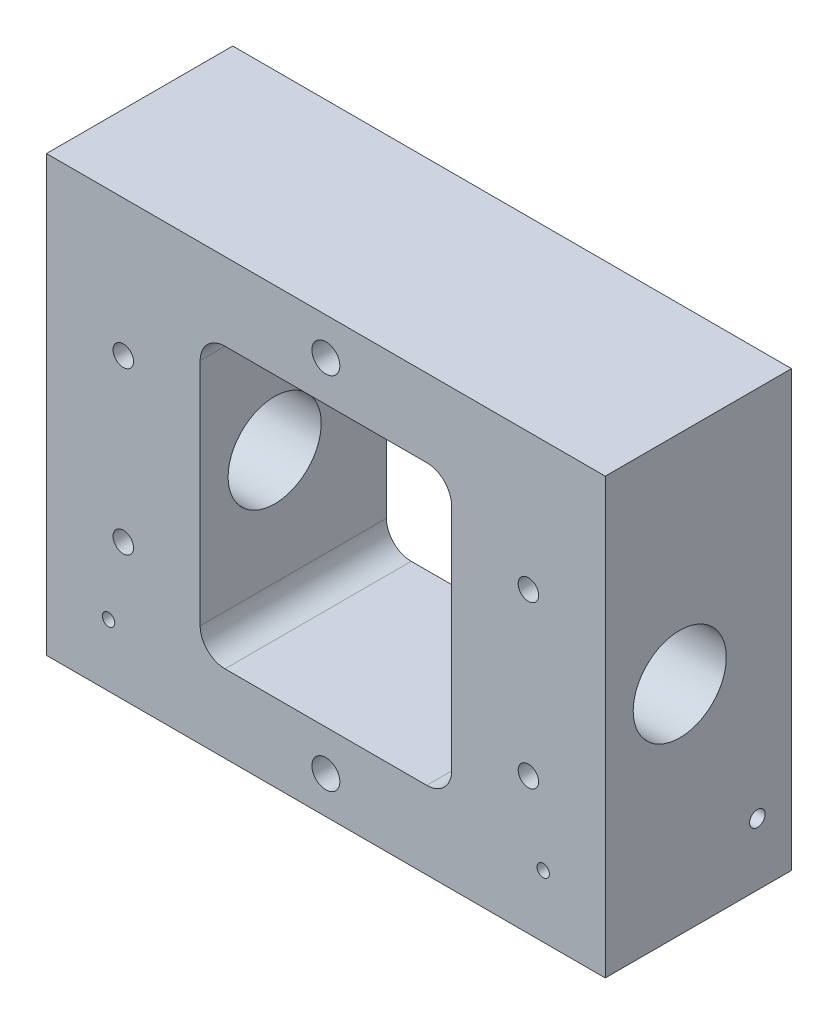
SolidWorks part; units mm, degrees
material "Lega 6061"
ref_plane "Piano frontale" through (0, 0, 0) normal (0, 0, 1) x (1, 0, 0)
ref_plane "Piano superiore" through (0, 0, 0) normal (0, 1, 0) x (1, 0, 0)
ref_plane "Piano destro" through (0, 0, 0) normal (1, 0, 0) x (0, 0, -1)
sketch "Schizzo1" plane through (0, 0, 0) normal (0, 0, 1) x (1, 0, 0)
  line L1 (0, 0) -> (90, 0)
  line L2 (0, 0) -> (0, 70)
  line L3 (0, 70) -> (90, 70)
  line L4 (90, 0) -> (90, 70)
  dimension "D1" = 90
  dimension "D2" = 70
extrude "Estrusione-Estrusione1" add sketch "Schizzo1" against normal blind 30
sketch "Schizzo2" plane through (0, 0, 0) normal (-1, 0, 0) x (0, 0, 1)
  line L0 (-30, 35) -> (0, 35) construction
  line L1 (-30, 70) -> (-30, 0) construction
  line L2 (0, 70) -> (0, 0) construction
  circle A0 centre (-12, 35) radius 7.5
  dimension "D1" = 15
  dimension "D2" = 18
extrude "Taglio-Estrusione1" cut sketch "Schizzo2" against normal through all
sketch "Schizzo3" plane through (0, 0, -30) normal (0, 0, -1) x (-1, 0, 0)
  line L0 (-94.314, 64) -> (4.9562, 64) construction
  line L2 (-90, 70) -> (0, 70) construction
  line L4 (-90, 35) -> (0, 35) construction
  line L5 (-90, 0) -> (-90, 70) construction
  line L6 (0, 70) -> (0, 0) construction
  line L7 (-94.314, 6) -> (4.9562, 6) construction
  line L8 (-45, 70) -> (-45, 0) construction
  line L9 (0, 0) -> (-90, 0) construction
  point P16 (-45, 64)
  point P17 (-45, 6)
  dimension "D1" = 6
hole_wizard "Foro lamato per Vite M4 a testa cilindrica piana-1" positions "Schizzo3D1" profile "Schizzo4" counterbore size "M4" standard "ISO" end condition through all
sketch3d "Schizzo3D1"
  line L0 (90, 70, -30) -> (0, 70, -30) construction
  point P0 (45, 64, -30)
  point P3 (45, 6, -30)
sketch "Schizzo4" plane through (45, 64, -30) normal (1, 0, 0) x (0, 1, 0)
  line L0 (0, 0) -> (0, 30)
  line L1 (0, 30) -> (2.25, 30)
  line L3 (2.25, 30) -> (2.25, 2.6)
  line L4 (2.25, 2.6) -> (4, 2.6)
  line L5 (4, 2.6) -> (4, 0)
  line L7 (4, 0) -> (0, 0)
  line L11 (0, -6.35) -> (0, 107.95) construction
  dimension "Thru Hole Dia." = 4.5
  dimension "Thru Hole Depth" = 30
  dimension "C'Bore Dia." = 8
  dimension "C'Bore Depth" = 2.6
ref_axis "Assi1" through (90, 35, -12) along (-1, 0, 0)
sketch "Schizzo14" plane through (0, 0, 0) normal (0, 0, 1) x (1, 0, 0)
  line L0 (45, 70) -> (45, 0) construction
  line L2 (61.25, 12.5) -> (28.75, 12.5)
  line L3 (65.25, 16.5) -> (65.25, 53.5)
  line L4 (90, 35) -> (0, 35) construction
  line L5 (61.25, 57.5) -> (28.75, 57.5)
  line L6 (24.75, 16.5) -> (24.75, 53.5)
  line L7 (65.25, 12.5) -> (24.75, 57.5) construction
  line L8 (65.25, 57.5) -> (24.75, 12.5) construction
  line L9 (0, 0) -> (90, 0) construction
  arc A0 (61.25, 57.5) -> (65.25, 53.5) centre (61.25, 53.5) cw
  arc A1 (65.25, 16.5) -> (61.25, 12.5) centre (61.25, 16.5) cw
  arc A2 (28.75, 12.5) -> (24.75, 16.5) centre (28.75, 16.5) cw
  arc A3 (24.75, 53.5) -> (28.75, 57.5) centre (28.75, 53.5) cw
  point P2 (45, 35)
  point P3 (45, 35)
  dimension "D1" = 4
  dimension "D2" = 45
  dimension "D3" = 40.5
  dimension "D4" = 12.5
extrude "Taglio-Estrusione4" cut sketch "Schizzo14" against normal through all
sketch "Schizzo16" plane through (0, 0, 0) normal (0, 0, 1) x (1, 0, 0)
  line L0 (45, 70) -> (45, 0) construction
  line L1 (0, 35) -> (90, 35) construction
  line L2 (0, 70) -> (0, 0) construction
  line L3 (0, 0) -> (90, 0) construction
  circle A0 centre (10, 10) radius 1
  circle A1 centre (80, 10) radius 1
  dimension "D1" = 2
  dimension "D2" = 10
  dimension "D3" = 10
extrude "Taglio-Estrusione6" cut sketch "Schizzo16" against normal through all
sketch "Schizzo17" plane through (0, 0, -30) normal (0, 0, -1) x (-1, 0, 0)
  line L0 (-45, 70) -> (-45, 0.5122) construction
  line L1 (-90, 70) -> (0, 70) construction
  line L2 (-45, 70) -> (-45, 0) construction
  line L3 (0, 35) -> (-90, 35) construction
  circle A0 centre (-10, 10) radius 8
  circle A1 centre (-80, 10) radius 8
  dimension "D1" = 16
extrude "Taglio-Estrusione8" cut sketch "Schizzo17" against normal blind 13
sketch "Schizzo18" plane through (0, 0, 0) normal (0, 0, 1) x (1, 0, 0)
  line L0 (0, 70) -> (90, 0) construction
  line L1 (90, 70) -> (0, 0) construction
  line L2 (45, 35) -> (45, 70) construction
  line L3 (12.375, 35.0996) -> (12.375, 74.2174) construction
  line L4 (24.75, 35) -> (0, 35) construction
  line L5 (24.75, 53.5) -> (24.75, 16.5) construction
  line L6 (90, 35) -> (0, 35) construction
  line L7 (90, 70) -> (0, 70) construction
  point P9 (12.375, 22)
  point P11 (45, 35)
  point P17 (12.375, 48)
  point P24 (77.625, 22)
  point P25 (77.625, 48)
  dimension "D1" = 13
hole_wizard "Foro filettato M4-1" positions "Schizzo20" profile "Schizzo19" tap size "M4" standard "ISO" end condition through all
sketch "Schizzo20" plane through (0, 0, 0) normal (0, 0, 1) x (1, 0, 0)
  point P0 (12.375, 48)
  point P3 (12.375, 22)
  point P6 (77.625, 48)
  point P9 (77.625, 22)
cosmetic thread "Filettatura del foro1" parameters "D2"=4
cosmetic thread "Filettatura del foro2" parameters "D2"=4
cosmetic thread "Filettatura del foro3" parameters "D2"=4
cosmetic thread "Filettatura del foro4" parameters "D2"=4
sketch "Schizzo19" plane through (12.375, 48, 0) normal (1, 0, 0) x (0, -1, 0)
  line L0 (0, 0) -> (0, 30)
  line L1 (0, 30) -> (1.65, 30)
  line L2 (1.65, 30) -> (1.65, 0)
  line L5 (1.65, 0) -> (0, 0)
  line L11 (0, -6.35) -> (0, 107.95) construction
  dimension "Thru Tap Drill Dia." = 3.3
  dimension "Thru Tap Drill Depth" = 30
sketch "Schizzo21" plane through (0, 0, -30) normal (0, 0, -1) x (-1, 0, 0)
  line L0 (-70, 73.919) -> (-70, -6.106) construction
  line L1 (-45, 70) -> (-45, 0) construction
  line L2 (-90, 70) -> (0, 0) construction
  line L3 (0, 70) -> (-90, 0) construction
  line L5 (-20, 72.5272) -> (-20, -6.106) construction
  point P6 (-70, 54.4444)
  point P9 (-70, 15.5556)
  point P14 (-20, 54.4444)
  point P15 (-20, 15.5556)
  dimension "D1" = 25
  dimension "D2" = 25
hole_wizard "Foro filettato M3-1" positions "Schizzo23" profile "Schizzo22" tap size "M3" standard "ISO"
sketch "Schizzo23" plane through (0, 0, -30) normal (0, 0, -1) x (-1, 0, 0)
  point P0 (-70, 54.4444)
  point P3 (-70, 15.5556)
  point P6 (-20, 54.4444)
  point P9 (-20, 15.5556)
sketch "Schizzo22" plane through (70, 54.4444, -30) normal (1, 0, 0) x (0, 1, 0)
  line L0 (0, 0) -> (0, 12.7511)
  line L1 (0, 12.7511) -> (1.25, 12)
  line L2 (1.25, 12) -> (1.25, 0)
  line L5 (1.25, 0) -> (0, 0)
  line L10 (0, 12.7511) -> (-1.25, 12) construction
  line L11 (0, -6.35) -> (0, 107.95) construction
  dimension "Tap Drill Dia." = 2.5
  dimension "Tap Drill Depth" = 12
  dimension "Drill Angle" = 118
cosmetic thread "Filettatura del foro5" parameters "D1"=8, "D2"=3
cosmetic thread "Filettatura del foro6" parameters "D1"=8, "D2"=3
cosmetic thread "Filettatura del foro7" parameters "D1"=8, "D2"=3
cosmetic thread "Filettatura del foro8" parameters "D1"=8, "D2"=3
sketch "Schizzo24" plane through (0, 0, 0) normal (-1, 0, 0) x (0, 0, 1)
  line L0 (-17, 18) -> (-17, 2) construction
  line L1 (-17, 10) -> (-30, 10) construction
  point P6 (-24.5, 10)
  dimension "D1" = 7.5
hole_wizard "Foro filettato M3-2" positions "Schizzo26" profile "Schizzo27" tap size "M3" standard "ISO" end condition up to next
sketch "Schizzo26" plane through (0, 0, 0) normal (-1, 0, 0) x (0, 0, 1)
  point P0 (-24.5, 10)
sketch "Schizzo27" plane through (0, 10, -24.5) normal (0, 1, 0) x (0, 0, 1)
  line L0 (0, 0) -> (0, 2)
  line L1 (0, 2) -> (1.25, 2)
  line L2 (1.25, 2) -> (1.25, 0)
  line L5 (1.25, 0) -> (0, 0)
  line L11 (0, -6.35) -> (0, 107.95) construction
  dimension "Thru Tap Drill Dia." = 2.5
  dimension "Thru Tap Drill Depth" = 2
cosmetic thread "Filettatura del foro9" parameters "D2"=3
sketch "Schizzo28" plane through (0, 0, 0) normal (0, -1, 0) x (1, 0, 0)
  line L0 (2, -17) -> (18, -17) construction
  line L1 (10, -17) -> (10, -30) construction
  line L2 (94.314, -30) -> (-4.9562, -30) construction
  point P8 (10, -24.5)
  dimension "D1" = 7.5
hole_wizard "Foro filettato M3-3" positions "Schizzo30" profile "Schizzo31" tap size "M3" standard "ISO" end condition up to next
sketch "Schizzo30" plane through (0, 0, 0) normal (0, -1, 0) x (-1, 0, 0)
  point P0 (-10, 24.5)
sketch "Schizzo31" plane through (10, 0, -24.5) normal (1, 0, 0) x (0, 0, -1)
  line L0 (0, 0) -> (0, 2)
  line L1 (0, 2) -> (1.25, 2)
  line L2 (1.25, 2) -> (1.25, 0)
  line L5 (1.25, 0) -> (0, 0)
  line L11 (0, -6.35) -> (0, 107.95) construction
  dimension "Thru Tap Drill Dia." = 2.5
  dimension "Thru Tap Drill Depth" = 2
cosmetic thread "Filettatura del foro10" parameters "D2"=3
sketch "Schizzo32" plane through (0, 0, 0) normal (0, -1, 0) x (1, 0, 0)
  line L0 (72, -17) -> (88, -17) construction
  line L1 (72, -17) -> (88, -17) construction
  line L2 (80, -17) -> (80, -30) construction
  line L3 (94.314, -30) -> (-4.9562, -30) construction
  point P9 (80, -24.5)
  dimension "D1" = 7.5
hole_wizard "Foro filettato M3-4" positions "Schizzo34" profile "Schizzo35" tap size "M3" standard "ISO" end condition up to next
sketch "Schizzo34" plane through (0, 0, 0) normal (0, -1, 0) x (-1, 0, 0)
  point P0 (-80, 24.5)
sketch "Schizzo35" plane through (80, 0, -24.5) normal (1, 0, 0) x (0, 0, -1)
  line L0 (0, 0) -> (0, 2)
  line L1 (0, 2) -> (1.25, 2)
  line L2 (1.25, 2) -> (1.25, 0)
  line L5 (1.25, 0) -> (0, 0)
  line L11 (0, -6.35) -> (0, 107.95) construction
  dimension "Thru Tap Drill Dia." = 2.5
  dimension "Thru Tap Drill Depth" = 2
cosmetic thread "Filettatura del foro11" parameters "D2"=3
sketch "Schizzo36" plane through (90, 0, 0) normal (1, 0, 0) x (0, 0, -1)
  line L0 (17, 18) -> (17, 2) construction
  line L1 (17, 10) -> (30, 10) construction
  point P8 (24.5, 10)
hole_wizard "Foro filettato M3-5" positions "Schizzo38" profile "Schizzo37" tap size "M3" standard "ISO" end condition up to next
sketch "Schizzo38" plane through (90, 0, 0) normal (1, 0, 0) x (0, 0, -1)
  point P0 (24.5, 10)
cosmetic thread "Filettatura del foro12" parameters "D2"=3
sketch "Schizzo37" plane through (90, 10, -24.5) normal (0, 1, 0) x (0, 0, -1)
  line L0 (0, 0) -> (0, 2)
  line L1 (0, 2) -> (1.25, 2)
  line L2 (1.25, 2) -> (1.25, 0)
  line L5 (1.25, 0) -> (0, 0)
  line L11 (0, -6.35) -> (0, 107.95) construction
  dimension "Thru Tap Drill Dia." = 2.5
  dimension "Thru Tap Drill Depth" = 2
